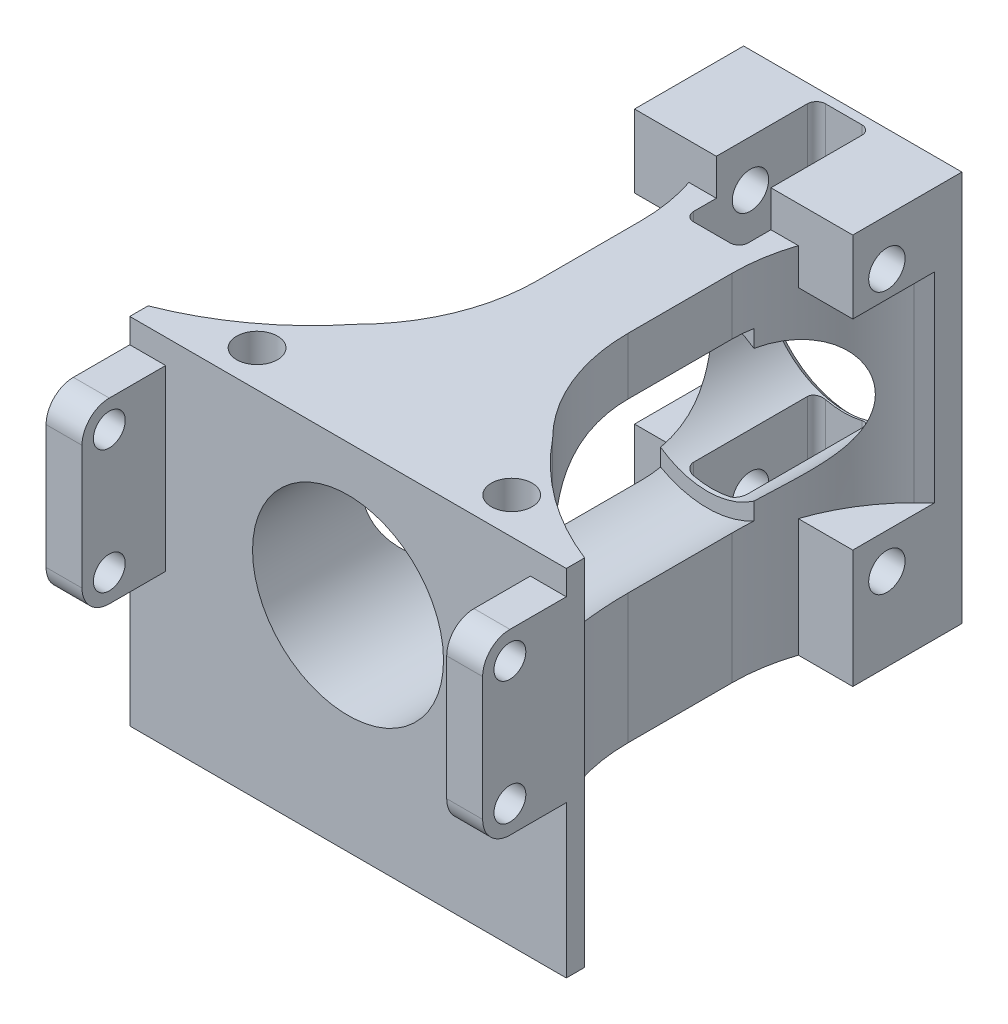
SolidWorks part; units mm, degrees
material "6061 合金"
ref_plane "前视基准面" through (0, 0, 0) normal (0, 0, 1) x (1, 0, 0)
ref_plane "上视基准面" through (0, 0, 0) normal (0, 1, 0) x (1, 0, 0)
ref_plane "右视基准面" through (0, 0, 0) normal (1, 0, 0) x (0, 0, -1)
sketch "草图1" plane through (0, 0, 0) normal (0, 0, 1) x (1, 0, 0)
  line L1 (-24, -15.5) -> (24, -15.5)
  line L2 (-24, -15.5) -> (-24, 15.5)
  line L3 (-24, 15.5) -> (24, 15.5)
  line L4 (24, -15.5) -> (24, 15.5)
  line L5 (-24, -15.5) -> (24, 15.5) construction
  line L6 (-24, 15.5) -> (24, -15.5) construction
  circle A0 centre (0, 0) radius 8.9
  point P0 (0, 0)
  dimension "D3" = 17.8
  dimension "D1" = 48
  dimension "D2" = 31
extrude "凸台-拉伸1" add sketch "草图1" along normal blind 65
sketch "草图2" plane through (0, 0, 65) normal (0, 0, 1) x (1, 0, 0)
  circle A0 centre (0, 0) radius 10.5
  dimension "D1" = 21
extrude "切除-拉伸1" cut sketch "草图2" against normal offset from surface (49 mm away) 16 up to face at (0, 0, 0)
sketch "草图4" plane through (0, 15.5, 0) normal (0, 1, 0) x (1, 0, 0)
  line L0 (-24, 9) -> (-10.8579, -4.1421)
  line L1 (-24, -65) -> (-24, 0) construction
  line L2 (-5, -18.2843) -> (-5, -29.7157)
  line L3 (-10.8579, -43.8579) -> (-24, -57) construction
  line L4 (-24, -57) -> (-24, 9) construction
  line L5 (0, 0) -> (0, -65) construction
  line L6 (24, -65) -> (-24, -65) construction
  line L7 (-24, -65) -> (-24, -62) construction
  line L8 (-24, -62) -> (-21, -62) construction
  line L9 (24, 0) -> (-24, 0) construction
  line L10 (10.8579, -43.8579) -> (24, -57) construction
  line L11 (5, -18.2843) -> (5, -29.7157)
  line L12 (24, 9) -> (10.8579, -4.1421)
  line L13 (24, -57) -> (24, 9) construction
  line L14 (35.5, -24) -> (-35.5, -24) construction
  line L15 (9.5, -2.5) -> (-9.5, -2.5) construction
  line L16 (24, -53.4842) -> (24, 9)
  line L17 (-24, -53.4842) -> (-24, 9)
  arc A2 (5, -18.2843) -> (10.8579, -4.1421) centre (25, -18.2843) cw
  arc A3 (10.8579, -43.8579) -> (5, -29.7157) centre (25, -29.7157) cw
  arc A4 (-5, -29.7157) -> (-10.8579, -43.8579) centre (-25, -29.7157) cw
  arc A5 (-10.8579, -4.1421) -> (-5, -18.2843) centre (-25, -18.2843) cw
  circle A6 centre (-35.5, -24) radius 30 construction
  circle A7 centre (35.5, -24) radius 30 construction
  circle A8 centre (9.5, -2.5) radius 1.2 construction
  circle A9 centre (-9.5, -2.5) radius 1.2 construction
  arc A10 (-10.8579, -43.8579) -> (-24, -53.4842) centre (-35.5, -24) cw
  arc A11 (10.8579, -43.8579) -> (24, -53.4842) centre (35.5, -24) ccw
  point P12 (-5, -24)
  point P26 (5, -10)
  point P29 (5, -38)
  point P32 (-5, -38)
  point P35 (-5, -10)
  point P36 (0, -24)
  point P41 (0, -2.5)
  dimension "D3" = 24
  dimension "D7" = 20
  dimension "D4" = 60
  dimension "D11" = 2.4
  dimension "D1" = 3
  dimension "D2" = 3
  dimension "D5" = 10
  dimension "D6" = 10
  dimension "D8" = 71
  dimension "D9" = 2.5
  dimension "D10" = 19
  dimension "D12" = 135
extrude "切除-拉伸3" cut sketch "草图4" against normal through all
sketch "草图6" plane through (0, 15.5, 0) normal (0, 1, 0) x (1, 0, 0)
  line L0 (0, 0) -> (0, -1) construction
  line L1 (-2, -1) -> (2, -1)
  line L2 (-3, -2) -> (-3, -14.5)
  line L3 (-2, -15.5) -> (2, -15.5)
  line L4 (3, -2) -> (3, -14.5)
  arc A0 (-3, -14.5) -> (-2, -15.5) centre (-2, -14.5) ccw
  arc A1 (2, -15.5) -> (3, -14.5) centre (2, -14.5) ccw
  arc A2 (2, -1) -> (3, -2) centre (2, -2) cw
  arc A3 (-2, -1) -> (-3, -2) centre (-2, -2) ccw
  point P9 (-3, -15.5)
  point P14 (3, -1)
  point P17 (-3, -1)
  dimension "D4" = 1
  dimension "D1" = 1
  dimension "D2" = 14.5
  dimension "D3" = 6
extrude "切除-拉伸5" cut sketch "草图6" along normal through all from surface starting at face at (0, -15.5, 30.7635)
sketch "草图9" plane through (0, 15.5, 0) normal (0, 1, 0) x (1, 0, 0)
  line L0 (9.5, -2.5) -> (-9.5, -2.5) construction
  line L1 (0, -2.5) -> (0, 0) construction
  circle A0 centre (9.5, -2.5) radius 1.5
  circle A1 centre (-9.5, -2.5) radius 1.5
  dimension "D3" = 3
  dimension "D1" = 2.5
  dimension "D2" = 19
extrude "切除-拉伸6" cut sketch "草图9" against normal blind 7
cosmetic thread "装饰螺纹线1" [suppressed] parameters "D2"=3
cosmetic thread "装饰螺纹线2" [suppressed] parameters "D2"=3
extrude "切除-拉伸7" cut sketch "草图9<2>" along normal blind 7 from surface starting at face at (0, -15.5, 8.25)
sketch "草图9<2>" plane through (0, 15.5, 0) normal (0, 1, 0) x (1, 0, 0) same geometry as "草图9"
cosmetic thread "装饰螺纹线3" parameters "D2"=3
cosmetic thread "装饰螺纹线4" parameters "D2"=3
sketch "草图12" plane through (0, -15.5, 0) normal (0, -1, 0) x (1, 0, 0)
  line L0 (-5, 18.2843) -> (5, 18.2843)
  line L12 (-15, 0) -> (15, 0)
  line L14 (15, 0) -> (10.8579, 4.1421)
  line L15 (5, 18.2843) -> (5, 29.7157)
  line L17 (24, 53.4842) -> (24, 65)
  line L18 (24, 65) -> (-24, 65)
  line L19 (-24, 65) -> (-24, 53.4842)
  line L21 (-5, 29.7157) -> (-5, 18.2843)
  line L22 (-10.8579, 4.1421) -> (-15, 0)
  line L24 (-15, 0) -> (15, 0) construction
  line L26 (15, 0) -> (10.8579, 4.1421) construction
  line L27 (5, 18.2843) -> (5, 29.7157)
  line L29 (24, 53.4842) -> (24, 65)
  line L30 (24, 65) -> (-24, 65)
  line L31 (-24, 65) -> (-24, 53.4842)
  line L33 (-5, 29.7157) -> (-5, 18.2843)
  line L34 (-10.8579, 4.1421) -> (-15, 0) construction
  arc A4 (5, 18.2843) -> (10.8579, 4.1421) centre (25, 18.2843) ccw
  arc A5 (10.8579, 43.8579) -> (5, 29.7157) centre (25, 29.7157) ccw
  arc A6 (-5, 29.7157) -> (-10.8579, 43.8579) centre (-25, 29.7157) ccw
  arc A7 (-10.8579, 4.1421) -> (-5, 18.2843) centre (-25, 18.2843) ccw
  arc A8 (5, 18.2843) -> (10.8579, 4.1421) centre (25, 18.2843) ccw construction
  arc A9 (10.8579, 43.8579) -> (5, 29.7157) centre (25, 29.7157) ccw
  arc A10 (-5, 29.7157) -> (-10.8579, 43.8579) centre (-25, 29.7157) ccw
  arc A11 (-10.8579, 4.1421) -> (-5, 18.2843) centre (-25, 18.2843) ccw construction
  arc A14 (24, 53.4842) -> (10.8579, 43.8579) centre (35.5, 24) ccw
  arc A15 (24, 53.4842) -> (10.8579, 43.8579) centre (35.5, 24) ccw
  arc A16 (-10.8579, 43.8579) -> (-24, 53.4842) centre (-35.5, 24) ccw
  arc A17 (-10.8579, 43.8579) -> (-24, 53.4842) centre (-35.5, 24) ccw
  dimension "D1" = 0
extrude "凸台-拉伸4" add sketch "草图12" along normal blind 8
sketch "草图11" plane through (0, 15.5, 0) normal (0, 1, 0) x (1, 0, 0)
  line L0 (14, -51.5) -> (-14, -51.5) construction
  line L1 (0, -51.5) -> (0, 0) construction
  circle A0 centre (14, -51.5) radius 2.25
  circle A1 centre (-14, -51.5) radius 2.25
  dimension "D3" = 4.5
  dimension "D1" = 51.5
  dimension "D2" = 28
extrude "切除-拉伸9" cut sketch "草图11" against normal through all
sketch "草图14" plane through (0, -23.5, 0) normal (0, -1, 0) x (1, 0, 0)
  line L0 (-5, 24) -> (5, 24) construction
  line L1 (-5, 29.7157) -> (-5, 18.2843) construction
  line L2 (5, 18.2843) -> (5, 29.7157) construction
  circle A0 centre (0, 24) radius 1.5
  dimension "D1" = 3
extrude "切除-拉伸10" cut sketch "草图14" against normal blind 11
cosmetic thread "装饰螺纹线9" parameters "D2"=4
sketch "草图15" plane through (0, 15.5, 0) normal (0, 1, 0) x (1, 0, 0)
  line L0 (24, -65) -> (-24, -65) construction
  line L1 (20.05, -65) -> (-20.05, -65)
  line L2 (20.05, -65) -> (20.05, -55.5)
  line L3 (20.05, -55.5) -> (-20.05, -55.5)
  line L4 (-20.05, -65) -> (-20.05, -55.5)
  line L5 (0, 0) -> (0, -55.5) construction
  circle A0 centre (-14, -51.5) radius 2.25 construction
  dimension "D1" = 40.1
  dimension "D2" = 4
extrude "切除-拉伸11" cut sketch "草图15" against normal through all
sketch "草图17" plane through (24, 0, 0) normal (1, 0, 0) x (0, 0, -1)
  line L0 (-53.4842, -23.5) -> (-65, -23.5) construction
  line L1 (-65, 15.5) -> (-53.4842, 15.5) construction
  line L2 (-61.7, 9.8) -> (-61.7, -3.8) construction
  line L3 (-61.7, 3) -> (-55.5, 3) construction
  line L4 (-55.5, -23.5) -> (-55.5, -6.8)
  line L5 (-55.5, -6.8) -> (-61.7, -6.8)
  line L6 (-64.7, -3.8) -> (-64.7, 9.8)
  line L9 (-64.7, 15.5) -> (-94.5, 15.5)
  line L10 (-94.5, 15.5) -> (-94.5, -23.5)
  line L11 (-94.5, -23.5) -> (-55.5, -23.5)
  line L12 (-55.5, -23.5) -> (-55.5, 15.5) construction
  line L13 (-61.7, 12.8) -> (-55.5, 12.8)
  line L14 (-55.5, 12.8) -> (-55.5, 15.5)
  line L15 (-55.5, 15.5) -> (-64.7, 15.5)
  circle A0 centre (-61.7, 9.8) radius 1.75
  circle A1 centre (-61.7, -3.8) radius 1.75
  arc A3 (-61.7, -6.8) -> (-64.7, -3.8) centre (-61.7, -3.8) cw
  arc A4 (-61.7, 12.8) -> (-64.7, 9.8) centre (-61.7, 9.8) ccw
  dimension "D3" = 3.5
  dimension "D4" = 3
  dimension "D1" = 13.6
  dimension "D2" = 6.2
  dimension "D6" = 12.5
extrude "切除-拉伸13" cut sketch "草图17" against normal through all
sketch "草图19" plane through (0, -15.5, 0) normal (0, -1, 0) x (1, 0, 0)
  line L0 (-10.8579, 4.1421) -> (-15, 0) construction
  line L1 (-15, 0) -> (-12, 0)
  line L2 (-15, 0) -> (-15, 3)
  line L3 (-15, 3) -> (-12, 3)
  line L4 (-12, 0) -> (-12, 3)
  line L5 (15, 0) -> (10.8579, 4.1421) construction
  line L6 (15, 0) -> (12, 0)
  line L7 (15, 0) -> (15, 3)
  line L8 (15, 3) -> (12, 3)
  line L9 (12, 0) -> (12, 3)
  dimension "D1" = 3
extrude "切除-拉伸14" cut sketch "草图19" against normal through all
chamfer "倒角1" distance 0.8 angle 45 1 edges at (8.9, 0, 0)
sketch "草图21" plane through (0, -15.5, 0) normal (0, -1, 0) x (1, 0, 0)
  line L0 (2, 1) -> (-2, 1) construction
  line L1 (-3, 2) -> (-3, 14.5) construction
  line L2 (-2, 15.5) -> (2, 15.5) construction
  line L3 (3, 14.5) -> (3, 2) construction
  line L4 (2, 1) -> (-2, 1)
  line L5 (-3, 2) -> (-3, 14.5)
  line L6 (-10.8579, 4.1421) -> (-12, 3)
  line L7 (-12, 3) -> (-12, 0)
  line L8 (-12, 0) -> (12, 0)
  line L9 (12, 0) -> (12, 3)
  line L10 (12, 3) -> (10.8579, 4.1421)
  line L11 (5, 18.2843) -> (-5, 18.2843)
  line L12 (-10.8579, 4.1421) -> (-12, 3)
  line L13 (-12, 3) -> (-12, 0)
  line L14 (-12, 0) -> (12, 0)
  line L15 (12, 0) -> (12, 3)
  line L16 (12, 3) -> (10.8579, 4.1421)
  line L17 (5, 18.2843) -> (-5, 18.2843)
  line L18 (-2, 15.5) -> (2, 15.5)
  line L19 (3, 14.5) -> (3, 2)
  arc A0 (-3, 2) -> (-2, 1) centre (-2, 2) ccw construction
  arc A1 (-2, 15.5) -> (-3, 14.5) centre (-2, 14.5) ccw construction
  arc A2 (5, 18.2843) -> (10.8579, 4.1421) centre (25, 18.2843) ccw
  arc A3 (-10.8579, 4.1421) -> (-5, 18.2843) centre (-25, 18.2843) ccw
  arc A4 (5, 18.2843) -> (10.8579, 4.1421) centre (25, 18.2843) ccw
  arc A5 (-10.8579, 4.1421) -> (-5, 18.2843) centre (-25, 18.2843) ccw
  arc A6 (3, 14.5) -> (2, 15.5) centre (2, 14.5) ccw construction
  arc A7 (2, 1) -> (3, 2) centre (2, 2) ccw construction
  arc A8 (-3, 2) -> (-2, 1) centre (-2, 2) ccw
  arc A9 (-2, 15.5) -> (-3, 14.5) centre (-2, 14.5) ccw
  arc A10 (3, 14.5) -> (2, 15.5) centre (2, 14.5) ccw
  arc A11 (2, 1) -> (3, 2) centre (2, 2) ccw
  circle A12 centre (9.5, 2.5) radius 1.5 construction
  circle A13 centre (-9.5, 2.5) radius 1.5 construction
  circle A14 centre (9.5, 2.5) radius 1.5
  circle A15 centre (-9.5, 2.5) radius 1.5
  dimension "D1" = 0
extrude "凸台-拉伸6" add sketch "草图21" along normal up to surface (8 mm away) up to face at (0, -23.5, 40.457)
sketch "草图22" plane through (0, -23.5, 0) normal (0, -1, 0) x (1, 0, 0)
  line L0 (12, 3) -> (12, 12)
  line L1 (12, 12) -> (6.013, 12)
  line L2 (12, 3) -> (10.8579, 4.1421) construction
  line L3 (12, 3) -> (10.8579, 4.1421)
  arc A0 (5, 18.2843) -> (10.8579, 4.1421) centre (25, 18.2843) ccw construction
  arc A1 (6.013, 12) -> (10.8579, 4.1421) centre (25, 18.2843) ccw
  dimension "D1" = 9
extrude "凸台-拉伸7" add sketch "草图22" against normal blind 13
mirror "镜向1" about plane through (0, 0, 0) normal (1, 0, 0) of "凸台-拉伸7"
sketch "草图23" plane through (0, 15.5, 0) normal (0, 1, 0) x (1, 0, 0)
  line L0 (-12, 0) -> (-12, -12)
  line L1 (-12, -12) -> (-3, -12)
  line L2 (-10.8579, -4.1421) -> (-12, -3) construction
  line L3 (-10.8579, -4.1421) -> (-12, -3)
  line L4 (-3, -2) -> (-3, -14.5) construction
  line L5 (12, 0) -> (-12, 0) construction
  line L6 (12, 0) -> (-12, 0)
  line L7 (-3, -12) -> (-3, -2)
  line L8 (2, -1) -> (-2, -1) construction
  line L9 (2, -1) -> (-2, -1)
  line L11 (12, 0) -> (12, -12)
  line L12 (12, -12) -> (6.013, -12)
  line L13 (6.013, -12) -> (3, -12)
  line L14 (3, -14.5) -> (3, -2) construction
  line L15 (3, -12) -> (3, -2)
  arc A0 (-6.013, -12) -> (-10.8579, -4.1421) centre (-25, -18.2843) ccw construction
  arc A1 (-6.013, -12) -> (-10.8579, -4.1421) centre (-25, -18.2843) ccw
  arc A2 (3, -2) -> (2, -1) centre (2, -2) ccw construction
  arc A3 (-2, -1) -> (-3, -2) centre (-2, -2) ccw construction
  arc A4 (3, -2) -> (2, -1) centre (2, -2) ccw
  arc A5 (-2, -1) -> (-3, -2) centre (-2, -2) ccw
  circle A6 centre (-9.5, -2.5) radius 1.5
  circle A7 centre (9.5, -2.5) radius 1.5
  dimension "D1" = 3
extrude "凸台-拉伸8" add sketch "草图23" along normal blind 4 and the other way blind 4 contours L1 L7 A5 L9 A4 L15 L13 L12 L11 L6 L0
sketch "草图20" plane through (0, 0, 0) normal (1, 0, 0) x (0, 0, -1)
  line L0 (0, 0) -> (-59.6656, 0) construction
  line L1 (-8.25, 0) -> (-8.25, 14.4) construction
  line L2 (-8.25, 0) -> (-8.25, -14.4) construction
  line L3 (-15.5, 15.5) -> (-15.5, 8.6724) construction
  line L4 (-15.5, 15.5) -> (-15.5, 8.6724) construction
  line L5 (-1, 19.5) -> (-1, 8.6724) construction
  line L6 (-1, 19.5) -> (-1, 8.6724) construction
  line L7 (-15.5, 12.0862) -> (-1, 12.0862) construction
  circle A0 centre (-8.25, 14.4) radius 2
  circle A1 centre (-8.25, -14.4) radius 2
  point P15 (-8.25, 12.0862)
  dimension "D2" = 4
  dimension "D1" = 14.4
extrude "切除-拉伸15" cut sketch "草图20" against normal through all both and the other way through all
